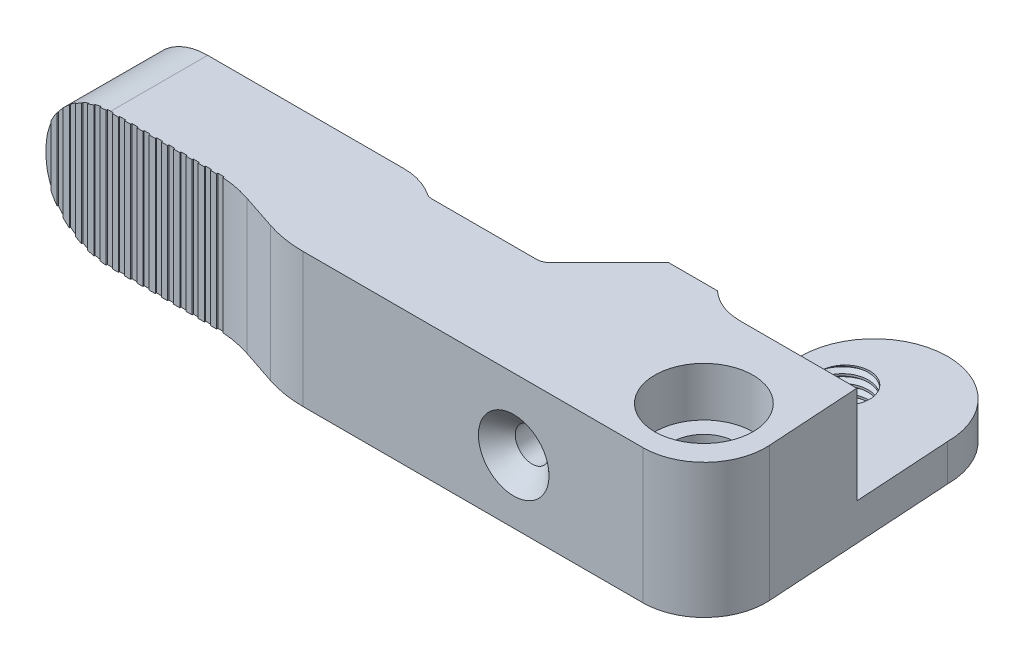
SolidWorks part; units mm, degrees
ref_plane "Front Plane" through (0, 0, 0) normal (0, 0, 1) x (1, 0, 0)
ref_plane "Top Plane" through (0, 0, 0) normal (0, 1, 0) x (1, 0, 0)
ref_plane "Right Plane" through (0, 0, 0) normal (1, 0, 0) x (0, 0, -1)
sketch "Sketch1" plane through (0, 0, 0) normal (0, 1, 0) x (1, 0, 0)
  line L0 (0, 0) -> (-34.63, 0)
  line L1 (-56, 9.95) -> (-56, 1.95)
  line L2 (-56, 1.95) -> (-40.5, 1.95)
  line L3 (-40.5, 1.95) -> (-34.63, 0)
  line L4 (-56, 9.95) -> (-33.25, 9.95)
  line L5 (-31.75, 8.95) -> (-22.5, 8.95)
  line L6 (-33.25, 9.95) -> (-31.75, 8.95)
  line L7 (-22.5, 8.95) -> (-15.7825, 15.6675)
  line L8 (-7.3, 0) -> (-7.3, 20.8) construction
  line L9 (-7.3, 20.8) -> (-1.3, 20.8) construction
  line L10 (-7.3, 20.8) -> (-13.3, 20.8) construction
  line L11 (-1.3, 20.8) -> (0, 0)
  arc A0 (-13.3, 20.8) -> (-1.3, 20.8) centre (-7.3, 20.8) cw
  arc A1 (-15.7825, 15.6675) -> (-13.3, 20.8) centre (-21.9155, 21.8006) ccw
  dimension "D14" = 20.8
  dimension "D1" = 34.63
  dimension "D2" = 8
  dimension "D3" = 9.95
  dimension "D4" = 56
  dimension "D5" = 15.5
  dimension "D6" = 22.75
  dimension "D7" = 9.25
  dimension "D8" = 33.5
  dimension "D9" = 1
  dimension "D10" = 135
  dimension "D11" = 9.5
  dimension "D12" = 6
  dimension "D15" = 7.3
  dimension "D16" = 6
extrude "Boss-Extrude1" add sketch "Sketch1" along normal blind 3
sketch "Sketch2" plane through (0, 3, 0) normal (0, 1, 0) x (1, 0, 0)
  line L0 (-0.8062, 12.9) -> (-10.3062, 12.9)
  line L1 (0, 0) -> (-1.3, 20.8) construction
  line L2 (-34.63, 0) -> (0, 0) construction
  line L3 (-17.35, 14.1) -> (-13.35, 14.1)
  line L4 (-15.7825, 15.6675) -> (-22.5, 8.95) construction
  line L5 (-0.8062, 12.9) -> (0, 0)
  line L6 (0, 0) -> (-34.63, 0)
  line L7 (-34.63, 0) -> (-40.5, 1.95)
  line L8 (-40.5, 1.95) -> (-56, 1.95)
  line L9 (-56, 1.95) -> (-56, 9.95)
  line L10 (-56, 9.95) -> (-33.25, 9.95)
  line L11 (-33.25, 9.95) -> (-31.75, 8.95)
  line L12 (-31.75, 8.95) -> (-22.5, 8.95)
  line L13 (-22.5, 8.95) -> (-17.35, 14.1)
  arc A0 (-10.3062, 12.9) -> (-13.35, 14.1) centre (-10.3062, 17.3602) cw
  dimension "D1" = 9.5
  dimension "D2" = 12.9
  dimension "D3" = 4
  dimension "D4" = 14.1
extrude "Boss-Extrude2" add sketch "Sketch2" along normal blind 7.95
fillet "Fillet1" radius 5.27 2 edges at (-56, 0, -5.95) (-56, 10.95, -5.95)
fillet "Fillet2" radius 5 1 edges at (0, 5.475, 0)
sketch "Sketch3" plane through (0, 10.95, 0) normal (0, 1, 0) x (1, 0, 0)
  line L1 (-34.63, 0) -> (-5.3223, 0) construction
  line L2 (-0.332, 5.3119) -> (-0.8062, 12.9) construction
  circle A0 centre (-5.9609, 5.6) radius 4
  dimension "D1" = 8
  dimension "D2" = 5.6
  dimension "D3" = 5.6
extrude "Cut-Extrude1" cut sketch "Sketch3" against normal blind 4
sketch "Sketch4" plane through (0, 6.95, 0) normal (0, 1, 0) x (1, 0, 0)
  circle A0 centre (-5.9609, 5.6) radius 2.575
  dimension "D1" = 5.15
extrude "Cut-Extrude2" cut sketch "Sketch4" against normal up to next
sketch "Sketch5" plane through (0, 3, 0) normal (0, 1, 0) x (1, 0, 0)
  line L0 (-0.8062, 12.9) -> (-1.3, 20.8) construction
  circle A0 centre (-9.4534, 20.6) radius 2
  circle A1 centre (-5.9609, 5.6) radius 2.575 construction
  dimension "D1" = 4
  dimension "D2" = 15
  dimension "D3" = 8.15
extrude "Cut-Extrude3" cut sketch "Sketch5" against normal up to next
sketch "Sketch6" plane through (0, 0, -1.95) normal (0, 0, 1) x (1, 0, 0)
  line L0 (-50.73, 10.95) -> (-40.5, 10.95) construction
  line L1 (-41.5, 10.95) -> (-42, 10.95)
  line L2 (-41.5, 10.95) -> (-41.5, 0)
  line L3 (-41.5, 0) -> (-42, 0)
  line L4 (-42, 10.95) -> (-42, 0)
  line L5 (-50.73, 0) -> (-40.5, 0) construction
  line L6 (-40.5, 10.95) -> (-40.5, 0) construction
  line L7 (-42.5, 10.95) -> (-42.5, 0)
  line L8 (-42.5, 10.95) -> (-43, 10.95)
  line L9 (-43, 10.95) -> (-43, 0)
  line L10 (-42.5, 0) -> (-43, 0)
  line L11 (-43.5, 10.95) -> (-43.5, 0)
  line L12 (-43.5, 10.95) -> (-44, 10.95)
  line L13 (-44, 10.95) -> (-44, 0)
  line L14 (-43.5, 0) -> (-44, 0)
  line L15 (-44.5, 10.95) -> (-44.5, 0)
  line L16 (-44.5, 10.95) -> (-45, 10.95)
  line L17 (-45, 10.95) -> (-45, 0)
  line L18 (-44.5, 0) -> (-45, 0)
  line L19 (-45.5, 10.95) -> (-45.5, 0)
  line L20 (-45.5, 10.95) -> (-46, 10.95)
  line L21 (-46, 10.95) -> (-46, 0)
  line L22 (-45.5, 0) -> (-46, 0)
  line L23 (-46.5, 10.95) -> (-46.5, 0)
  line L24 (-46.5, 10.95) -> (-47, 10.95)
  line L25 (-47, 10.95) -> (-47, 0)
  line L26 (-46.5, 0) -> (-47, 0)
  line L27 (-47.5, 10.95) -> (-47.5, 0)
  line L28 (-47.5, 10.95) -> (-48, 10.95)
  line L29 (-48, 10.95) -> (-48, 0)
  line L30 (-47.5, 0) -> (-48, 0)
  line L31 (-48.5, 10.95) -> (-48.5, 0)
  line L32 (-48.5, 10.95) -> (-49, 10.95)
  line L33 (-49, 10.95) -> (-49, 0)
  line L34 (-48.5, 0) -> (-49, 0)
  line L35 (-49.5, 10.95) -> (-49.5, 0)
  line L36 (-49.5, 10.95) -> (-50, 10.95)
  line L37 (-50, 10.95) -> (-50, 0)
  line L38 (-49.5, 0) -> (-50, 0)
  line L39 (-50.5, 10.95) -> (-50.5, 0)
  line L40 (-50.5, 10.95) -> (-51, 10.95)
  line L41 (-51, 10.95) -> (-51, 0)
  line L42 (-50.5, 0) -> (-51, 0)
  line L43 (-51.5, 10.95) -> (-51.5, 0)
  line L44 (-51.5, 10.95) -> (-52, 10.95)
  line L45 (-52, 10.95) -> (-52, 0)
  line L46 (-51.5, 0) -> (-52, 0)
  line L47 (-52.5, 10.95) -> (-52.5, 0)
  line L48 (-52.5, 10.95) -> (-53, 10.95)
  line L49 (-53, 10.95) -> (-53, 0)
  line L50 (-52.5, 0) -> (-53, 0)
  line L51 (-53.5, 10.95) -> (-53.5, 0)
  line L52 (-53.5, 10.95) -> (-54, 10.95)
  line L53 (-54, 10.95) -> (-54, 0)
  line L54 (-53.5, 0) -> (-54, 0)
  line L55 (-54.5, 10.95) -> (-54.5, 0)
  line L56 (-54.5, 10.95) -> (-55, 10.95)
  line L57 (-55, 10.95) -> (-55, 0)
  line L58 (-54.5, 0) -> (-55, 0)
  line L59 (-55.5, 10.95) -> (-55.5, 0)
  line L60 (-55.5, 10.95) -> (-56, 10.95)
  line L61 (-56, 10.95) -> (-56, 0)
  line L62 (-55.5, 0) -> (-56, 0)
  line L63 (-41.5, 10.95) -> (-42.5, 10.95) construction
  dimension "D1" = 0.5
  dimension "D2" = 1
  dimension "D4" = 1
  dimension "D3" = 15
extrude "Cut-Extrude4" cut sketch "Sketch6" against normal blind 0.1
fillet "Fillet3" radius 10 2 edges at (-34.63, 5.475, 0) (-40.5, 5.475, -1.95)
fillet "Fillet4" radius 5 1 edges at (-33.25, 5.475, -9.95)
fillet "Fillet5" radius 1 2 edges at (-22.5, 5.475, -8.95) (-31.75, 5.475, -8.95)
sketch "Sketch8" plane through (0, 0, -14.1) normal (0, 0, -1) x (-1, 0, 0)
  line L0 (15.7825, 0) -> (22.2071, 0) construction
  line L1 (17.35, 10.95) -> (17.35, 3) construction
  circle A0 centre (15.85, 5.15) radius 1.375
  dimension "D1" = 5.15
  dimension "D2" = 1.5
  dimension "D3" = 2.75
extrude "Cut-Extrude5" cut sketch "Sketch8" against normal up to next
chamfer "Chamfer1" distance 0.1 angle 45 1 edges at (-17.225, 5.15, -14.1)
chamfer "Chamfer2" distance 1.5 angle 45 1 edges at (-17.225, 5.15, 0)
sketch "Sketch9" plane through (0, 0, -9.95) normal (0, 0, -1) x (-1, 0, 0)
  line L0 (34.7639, 5.475) -> (56, 5.68) construction
  line L1 (34.7639, 10.95) -> (34.7639, 0) construction
  circle A1 centre (36.7639, 5.4943) radius 1.5
  dimension "D1" = 3
  dimension "D2" = 2
extrude "Cut-Extrude6" cut sketch "Sketch9" against normal blind 5
thread "Thread1" pitch 0.5 method cut profile "Thread Profile2" start angle 0, offset 0, length 0, pitch 0.5, diameter 3
ref_plane "Plane2" through (-35.2639, 5.4943, -9.95) normal (0, -1, 0) x (1, 0, 0)
sketch "Thread Profile2" plane through (-35.2639, 5.4943, -9.95) normal (0, -1, 0) x (1, 0, 0)
  line L0 (0, 0) -> (0, 0.5) construction
  line L1 (0, 0) -> (0.2706, 0.1562)
  line L2 (0.2706, 0.1562) -> (0.2706, 0.2187)
  line L3 (0.2706, 0.2187) -> (0, 0.375)
  line L4 (0.2706, 0.1875) -> (0, 0.1875) construction
  line L11 (0, 0) -> (0, 0.375)
  point P2 (0, 0)
  dimension "Pitch" = 0.5
  dimension "Profile_Angle" = 60
  dimension "Profile_Land" = 0.0625
  dimension "Profile_Height" = 0.2706
thread "Thread2" pitch 0.7 method cut profile "Thread Profile3" start angle 0, offset 0, length 0, pitch 0.7, diameter 4
ref_plane "Plane3" through (-11.4534, 3, -20.6) normal (0, 0, 1) x (-1, 0, 0)
sketch "Thread Profile3" plane through (-11.4534, 3, -20.6) normal (0, 0, 1) x (-1, 0, 0)
  line L0 (0, 0) -> (0, 0.7) construction
  line L1 (0, 0) -> (0.3789, 0.2187)
  line L2 (0.3789, 0.2187) -> (0.3789, 0.3062)
  line L3 (0.3789, 0.3062) -> (0, 0.525)
  line L4 (0.3789, 0.2625) -> (0, 0.2625) construction
  line L11 (0, 0) -> (0, 0.525)
  point P2 (0, 0)
  dimension "Pitch" = 0.7
  dimension "Profile_Angle" = 60
  dimension "Profile_Land" = 0.0875
  dimension "Profile_Height" = 0.3789
